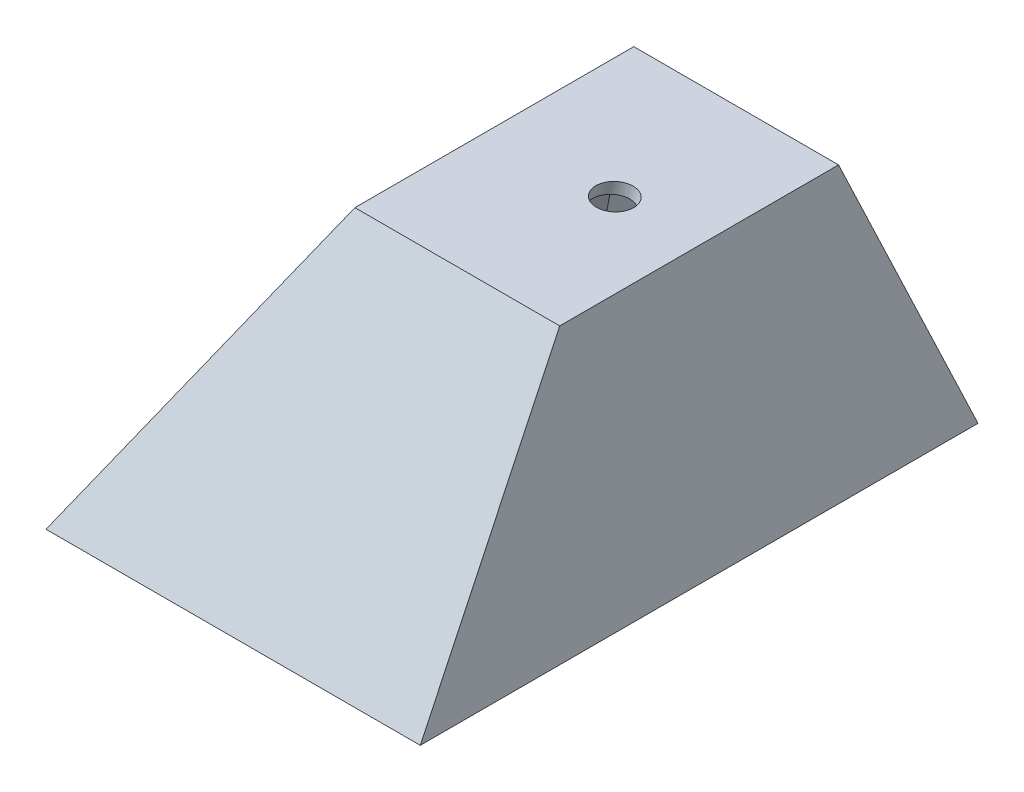
SolidWorks part; units mm, degrees
ref_plane "正面" through (0, 0, 0) normal (0, 0, 1) x (1, 0, 0)
ref_plane "平面" through (0, 0, 0) normal (0, 1, 0) x (1, 0, 0)
ref_plane "右側面" through (0, 0, 0) normal (1, 0, 0) x (0, 0, -1)
sketch "ｽｹｯﾁ1" plane through (0, 0, 0) normal (0, 0, 1) x (1, 0, 0)
  line L0 (-39.5058, -32.3901) -> (11.4942, -32.3901)
  line L1 (11.4942, -32.3901) -> (11.4942, 7.6099)
  line L2 (11.4942, 7.6099) -> (-16.4118, 7.6099)
  line L3 (-16.4118, 7.6099) -> (-39.5058, -32.3901)
  line L4 (-16.4118, 7.6099) -> (-39.5058, -32.3901)
  line L5 (11.4942, -32.3901) -> (11.4942, 7.6099)
  dimension "D1" = 60
  dimension "D2" = 51
  dimension "D3" = 40
extrude "ﾎﾞｽ - 押し出し1" add sketch "ｽｹｯﾁ1" along normal blind 76 contours L2 L3 L0 L1 region at (-8.7955, -14.3412, 0)
sketch "ｽｹｯﾁ2" plane through (11.4942, 0, 0) normal (1, 0, 0) x (0, 0, -1)
  line L0 (-57, 7.6099) -> (-76, -32.3901)
  line L1 (-76, 7.6099) -> (0, 7.6099) construction
  line L2 (-76, -32.3901) -> (-76, 7.6099)
  line L3 (-76, 7.6099) -> (-57, 7.6099)
  line L4 (-19, 7.6099) -> (0, -32.3901)
  line L5 (0, -32.3901) -> (0, 7.6099)
  line L6 (0, 7.6099) -> (-19, 7.6099)
  dimension "D1" = 19
  dimension "D2" = 19
extrude "ｶｯﾄ - 押し出し1" cut sketch "ｽｹｯﾁ2" against normal through all
shell "ｼｪﾙ2" thickness 1.75 removed face at (-14.0058, -32.3901, 38)
sketch "ｽｹｯﾁ4" plane through (0, 7.6099, 0) normal (0, 1, 0) x (1, 0, 0)
  line L1 (-16.4118, -57) -> (11.4942, -57) construction
  circle A0 centre (0, -38) radius 2.5
  point P2 (0, 0)
  dimension "D1" = 5
  dimension "D2" = 19
ref_plane "平面2" through (-3.2619, 0.874, 0) normal (0.9659, -0.2588, 0) x (0, 0, -1)
sketch "ｽｹｯﾁ6" plane through (-3.2619, 0.874, 0) normal (0.9659, -0.2588, 0) x (0, 0, -1)
  line L0 (-38.0891, 12.8856) -> (-38.0891, -10.2879)
ref_plane "平面3" through (0, 0, 38) normal (0, 0, -1) x (-1, 0, 0)
ref_plane "平面4" through (1.9025, 7.1002, 0) normal (0.2588, 0.9659, 0) x (0.9659, -0.2588, 0)
sketch "ｽｹｯﾁ7" plane through (1.9025, 7.1002, 0) normal (0.2588, 0.9659, 0) x (0.9659, -0.2588, 0)
  circle A0 centre (-1.9696, -38) radius 2.5
  dimension "D1" = 5
extrude "ｶｯﾄ - 押し出し3" cut sketch "ｽｹｯﾁ7" against normal through all
extrude "ｶｯﾄ - 押し出し4" cut sketch "ｽｹｯﾁ7<2>" along normal blind 3
sketch "ｽｹｯﾁ7<2>" plane through (1.9025, 7.1002, 0) normal (0.2588, 0.9659, 0) x (0.9659, -0.2588, 0) same geometry as "ｽｹｯﾁ7"
